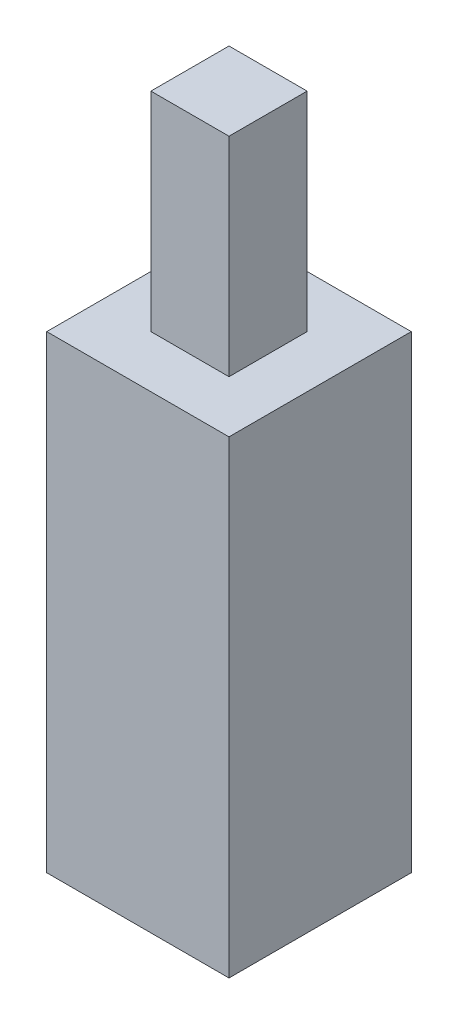
SolidWorks part; units mm, degrees
ref_plane "Front Plane" through (0, 0, 0) normal (0, 0, 1) x (1, 0, 0)
ref_plane "Top Plane" through (0, 0, 0) normal (0, 1, 0) x (1, 0, 0)
ref_plane "Right Plane" through (0, 0, 0) normal (1, 0, 0) x (0, 0, -1)
sketch "Sketch1" plane through (0, 0, 0) normal (0, 1, 0) x (1, 0, 0)
  line L1 (0, 0) -> (7, 0)
  line L2 (0, 0) -> (0, 7)
  line L3 (0, 7) -> (7, 7)
  line L4 (7, 0) -> (7, 7)
  dimension "D1" = 7
  dimension "D2" = 7
extrude "Boss-Extrude1" add sketch "Sketch1" along normal blind 18
sketch "Sketch2" plane through (0, 18, 0) normal (0, 1, 0) x (1, 0, 0)
  line L0 (7, 7) -> (0, 7) construction
  line L1 (2, 2) -> (5, 2)
  line L2 (2, 2) -> (2, 5)
  line L3 (2, 5) -> (5, 5)
  line L4 (5, 2) -> (5, 5)
  line L5 (0, 7) -> (0, 0) construction
  dimension "D1" = 3
  dimension "D2" = 3
  dimension "D3" = 2
  dimension "D4" = 2
extrude "Boss-Extrude2" add sketch "Sketch2" along normal blind 8
sketch "Sketch3" plane through (0, 0, 0) normal (0, -1, 0) x (-1, 0, 0)
  line L0 (0, 0) -> (-7, 0) construction
  line L1 (-6, 2.175) -> (-1, 2.175)
  line L2 (-6, 2.175) -> (-6, 4.825)
  line L3 (-6, 4.825) -> (-1, 4.825)
  line L4 (-1, 2.175) -> (-1, 4.825)
  line L5 (-6, 2.175) -> (-1, 4.825) construction
  line L6 (-6, 4.825) -> (-1, 2.175) construction
  line L7 (-7, 0) -> (-7, 7) construction
  point P0 (-3.5, 3.5)
  dimension "D1" = 3.5
  dimension "D2" = 2.65
  dimension "D3" = 5
  dimension "D4" = 3.5
extrude "Cut-Extrude1" cut sketch "Sketch3" against normal blind 1
